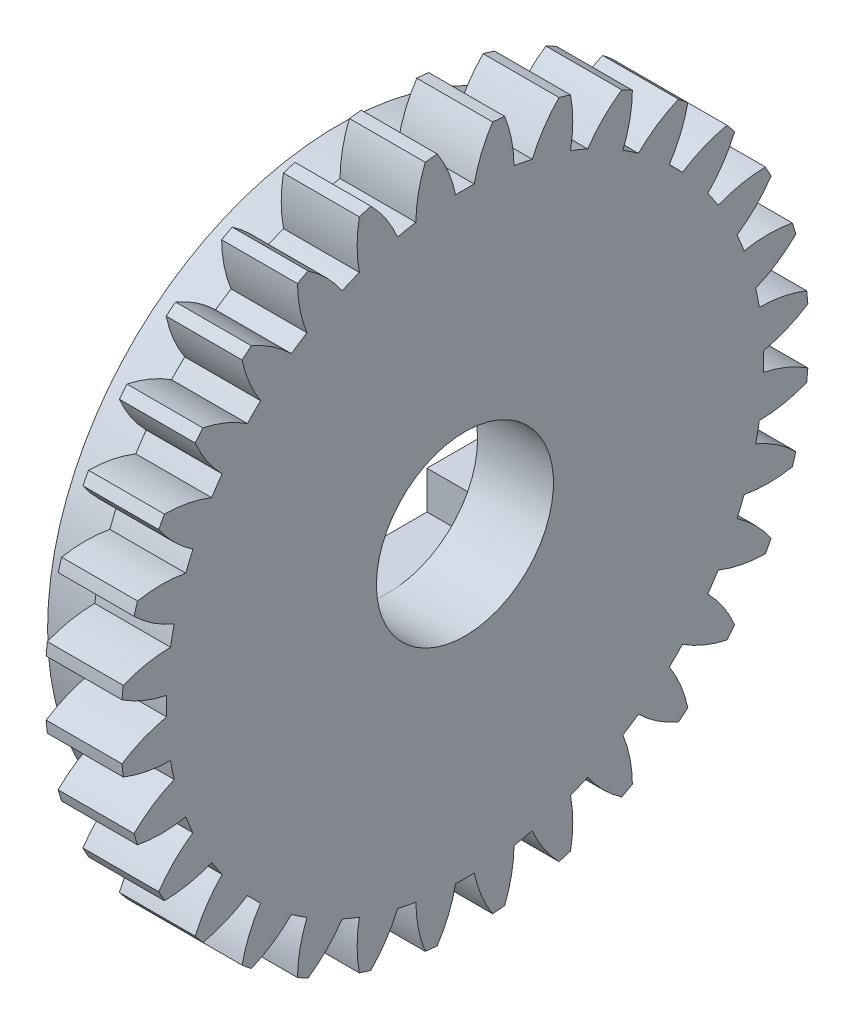
SolidWorks part; units mm, degrees
ref_plane "Plane1" through (0, 0, 0) normal (0, 0, 1) x (1, 0, 0)
ref_plane "Plane2" through (0, 0, 0) normal (0, 1, 0) x (1, 0, 0)
ref_plane "Plane3" through (0, 0, 0) normal (1, 0, 0) x (0, 0, -1)
other "Configuration Table"
sketch "HoldingSke" plane through (0, 0, 0) normal (0, 1, 0) x (1, 0, 0)
  line L0 (0, 0) -> (1.0601, -0.6624)
  line L1 (-15, 0) -> (100, 0) construction
  line L2 (0, 0) -> (-2.1039, 2.3779)
  line L3 (0, 0) -> (-11.863, 4.5341)
  line L4 (0, 0) -> (7.3237, 4.5764)
  line L5 (0, 0) -> (-46.8476, -17.4728)
  line L6 (0, 0) -> (-2.4869, -1.6779)
  line L7 (-2.1039, 2.3779) -> (8.6586, 51.2059)
  line L8 (-76.2, 54.61) -> (-76.1, 54.61)
  line L9 (-71.009, 38.7566) -> (-53.1078, 45.2721)
  line L10 (-76.2, 71.12) -> (104.1128, 71.12)
  line L11 (0, 0) -> (-3, 0)
  line L12 (-76.2, 101.6) -> (-76.17, 101.6)
  line L13 (24.9733, 27.94) -> (52.9518, 28.4284)
  line L14 (24.9733, 27.94) -> (24.9743, 27.94)
  line L15 (24.9733, 27.94) -> (100.4006, 29.5858)
  line L16 (-63.627, -0.8) -> (-12.827, -0.8)
  circle A0 centre (0, 0) radius 0.5
  circle A1 centre (0, 0) radius 11.799
  circle A2 centre (0, 0) radius 37.5
  circle A3 centre (0, 0) radius 0.5
  dimension "MHD" = 23.598
  dimension "Hub_dia" = 75
  dimension "Bore" = 1
  dimension "MBD" = 1
  dimension "Num_teeth" = 32
  dimension "Pitch" = 1.25
  dimension "Overall_len" = 50
  dimension "Show_teeth" = 32
  dimension "Thickness" = 3
  dimension "OAL" = 50.0001
  dimension "T_dim" = 0.1
  dimension "Ap" = 20
  dimension "H" = 19.05
  dimension "Pitch_radius" = 180.3128
  dimension "Width" = 3
  dimension "Backlash" = 0.03
  dimension "Addendum_fac" = 1
  dimension "Dedendum_fac" = 1.25
  dimension "Clearance_fac" = 0.25
  dimension "Dedendum_add" = 0.001
  dimension "Module" = 0.8
sketch "BasProSke" plane through (0, 0, 0) normal (0, 1, 0) x (1, 0, 0)
  line L0 (-10, 0) -> (60, 0) construction
  line L1 (0, 0) -> (0, 13.6)
  line L2 (0, 0) -> (3, 0)
  line L3 (3, 0) -> (3, 13.6)
  line L4 (3, 13.6) -> (0, 13.6)
  dimension "Thickness" = 3
  dimension "Diameter" = 27.2
revolve "Base-Revolve" add sketch "BasProSke" angle 360 about L0
sketch "TooCutSke" plane through (0, 0, 0) normal (1, 0, 0) x (0, 0, -1)
  line L1 (0, 0) -> (0, 107) construction
  line L2 (0, 0) -> (-0.6806, 12.7819) construction
  line L3 (0, 0) -> (-2.5067, 25.451) construction
  line L4 (-0.6806, 12.7819) -> (-1.2534, 12.7255) construction
  arc A0 (0.3689, 11.7932) -> (-0.3689, 11.7932) centre (0, 0) ccw
  arc A1 (1.1118, 13.58) -> (-1.1118, 13.58) centre (0, 0) ccw
  circle A2 centre (0, 0) radius 12.8 construction
  circle A3 centre (0, 0) radius 12.0281 construction
  arc A4 (-0.3689, 11.7932) -> (-1.1118, 13.58) centre (-5.3829, 10.7564) ccw
  arc A5 (1.1118, 13.58) -> (0.3689, 11.7932) centre (5.3829, 10.7564) ccw
  dimension "Root_dia" = 23.598
  dimension "Overcut_dia" = 27.2508
  dimension "Pitch_dia" = 25.6
  dimension "Base_dia" = 24.0561
  dimension "Flank_rad" = 5.12
  dimension "Half_ang" = 5.625
  dimension "Half_CT" = 0.5756
extrude "ToothCut" cut sketch "TooCutSke" along normal through all
fillet "Breaks" [suppressed] radius 0.016 tangent propagation no
fillet "RootFillets" [suppressed] radius 0.201
pattern_circular "TeethCuts" count 32 every 11.25 about axis through (-10, 0, 0) along (1, 0, 0) of "ToothCut", "RootFillets", "Breaks"
sketch "HubNeaOneSke" plane through (0, 0, 0) normal (-1, 0, 0) x (0, 0, 1)
  circle A0 centre (0, 0) radius 11.799
  dimension "Diameter" = 23.598
extrude "HubNearOne" [suppressed] add sketch "HubNeaOneSke" along normal blind 47.0001
sketch "HubNeaBotSke" plane through (0, 0, 0) normal (-1, 0, 0) x (0, 0, 1)
  circle A0 centre (0, 0) radius 11.799
  dimension "Diameter" = 23.598
extrude "HubNearBoth" [suppressed] add sketch "HubNeaBotSke" along normal blind 23.5
ref_plane "FarPln" through (3, 0, 0) normal (1, 0, 0) x (0, 0, -1)
sketch "HubFarSke" plane through (3, 0, 0) normal (1, 0, 0) x (0, 0, -1)
  circle A0 centre (0, 0) radius 11.799
  dimension "Diameter" = 23.598
extrude "HubFar" [suppressed] add sketch "HubFarSke" along normal blind 23.5
sketch "BorSke" plane through (0, 0, 0) normal (1, 0, 0) x (0, 0, -1)
  circle A0 centre (0, 0) radius 0.5
  dimension "Diameter" = 1
extrude "Bore" cut sketch "BorSke" along normal mid plane 100.0001
sketch "KeySke" plane through (0, 0, 0) normal (1, 0, 0) x (0, 0, -1)
  line L0 (-0.05, 0) -> (-0.05, 0.6)
  line L1 (-0.05, 0.6) -> (0.05, 0.6)
  line L2 (0.05, 0.6) -> (0.05, 0)
  line L3 (0, 0) -> (0, 34) construction
  line L4 (-0.05, 0) -> (0.05, 0)
  dimension "Offset" = 0.6
extrude "Keyway" [suppressed] cut sketch "KeySke" along normal mid plane 100.0001
pattern_circular "Keyway2" [suppressed] count 2 every 90 about axis through (-10, 0, 0) along (1, 0, 0) reverse direction yes
ref_axis "基准轴1" through (0, 0, 0) along (1, 0, 0)
sketch "草图2" plane through (0, 0, 0) normal (1, 0, 0) x (0, 0, -1)
  circle A1 centre (0, 0) radius 11.5
  dimension "D2" = 23
extrude "凸台-拉伸1" add sketch "草图2" against normal blind 2
sketch "草图1" plane through (-2, 0, 0) normal (1, 0, 0) x (0, 0, -1)
  line L0 (-6.3, 0) -> (6.3, 0) construction
  line L2 (-3.5, 3.5) -> (3.5, 3.5)
  line L3 (-3.5, 3.5) -> (-3.5, -3.5)
  line L4 (-3.5, -3.5) -> (3.5, -3.5)
  line L5 (3.5, 3.5) -> (3.5, -3.5)
  line L6 (-3.5, 3.5) -> (3.5, -3.5) construction
  line L7 (-3.5, -3.5) -> (3.5, 3.5) construction
  line L8 (-6.3, 2) -> (6.3, 2)
  line L9 (-6.3, -2) -> (6.3, -2)
  arc A9 (-6.3, 2) -> (-6.3, -2) centre (-6.3, 0) ccw
  arc A10 (6.3, -2) -> (6.3, 2) centre (6.3, 0) ccw
  point P0 (0, 0)
  point P8 (0, 0)
  point P13 (15.8938, 0)
  point P14 (0, 0)
  point P15 (8.3, 0)
  point P16 (0, 0)
  point P17 (0, 0)
  point P18 (-8.3, 0)
  dimension "D1" = 7
  dimension "D2" = 4
  dimension "D3" = 16.6
extrude "切除-拉伸1" cut sketch "草图1" along normal blind 2 contours L8 L3 L2 L5 | A10 L9 L5 L8 | L9 L3 L8 L5 | A9 L8 L3 L9 | L3 L9 L5 L4 region at (-2, 2.75, 0) region at (-2, 0, 0) region at (-2, 0, 5.7082) region at (-2, 0, -5.7082) region at (-2, -2.75, 0)
sketch "草图3" plane through (0, 0, 0) normal (-1, 0, 0) x (0, 0, 1)
  circle A0 centre (0, 0) radius 3.5
  dimension "D1" = 7
extrude "切除-拉伸2" cut sketch "草图3" against normal through all
equation "' \"Module@HoldingSke\" = 6.35"
equation "' \"Num_teeth@HoldingSke\" = 12"
equation "' \"Ap@HoldingSke\" =  20"
equation "' \"Ap@HoldingSke\" = 20"
equation "' \"Width@HoldingSke\" = 0.5 * 25.4"
equation "' \"Hub_dia@HoldingSke\"= 1 * 25.4"
equation "' \"Hub_dia@HoldingSke\" = 1 * 25.4"
equation "' \"Overall_len@HoldingSke\" = 1.0 * 25.4"
equation "' \"Bore@HoldingSke\" = 0.75 * 25.4"
equation "' \"T_dim@HoldingSke\" = 0.1 * 25.4"
equation "' \"Width@KeySke\" = 0.25 * 25.4"
equation "' \"Show_teeth@HoldingSke\" = 13"
equation "' \"Backlash@HoldingSke\" = 0.009 * 25.4"
equation "' \"Addendum_fac@HoldingSke\" = 1.0"
equation "' \"Dedendum_fac@HoldingSke\" = 1.25"
equation "' \"Dedendum_add@HoldingSke\" = 0.00005 * 25.4"
equation "' \"Clearance_fac@HoldingSke\" = 0.25"
equation "\"Pitch@HoldingSke\" = 1 / \"Module@HoldingSke\""
equation "\"Overcut_dia@TooCutSke\" = (\"Num_teeth@HoldingSke\" + 2 * \"Addendum_fac@HoldingSke\") / \"Pitch@HoldingSke\" + 0.002 * 25.4"
equation "\"Pitch_dia@TooCutSke\" = \"Num_teeth@HoldingSke\" / \"Pitch@HoldingSke\""
equation "\"Base_dia@TooCutSke\" = \"Num_teeth@HoldingSke\" / \"Pitch@HoldingSke\" * cos((\"Ap@HoldingSke\"  * 3.14159265 / 180))"
equation "\"Root_dia@TooCutSke\" = (\"Num_teeth@HoldingSke\" + 2) / \"Pitch@HoldingSke\" - 2 * (\"Addendum_fac@HoldingSke\" + \"Dedendum_fac@HoldingSke\") / \"Pitch@HoldingSke\" - \"Dedendum_add@HoldingSke\" * 2"
equation "\"Half_ang@TooCutSke\" = 180 / \"Num_teeth@HoldingSke\""
equation "\"Half_CT@TooCutSke\" = \"Num_teeth@HoldingSke\" / \"Pitch@HoldingSke\" * sin((3.14159265 / 2 / \"Num_teeth@HoldingSke\")) / 2 - 7 * \"Backlash@HoldingSke\" / 4"
equation "\"Flank_rad@TooCutSke\" = \"Num_teeth@HoldingSke\" / \"Pitch@HoldingSke\" / 5"
equation "\"Radius@RootFillets\" = \"Clearance_fac@HoldingSke\" / \"Pitch@HoldingSke\" + \"Dedendum_add@HoldingSke\""
equation "\"Break_rad@Breaks\" = 0.02 / \"Pitch@HoldingSke\""
equation "\"Thickness@HoldingSke\" = \"Width@HoldingSke\""
equation "\"OAL@HoldingSke\" = \"Thickness@HoldingSke\""
equation "\"MHD@HoldingSke\" = (\"Num_teeth@HoldingSke\" + 2) / \"Pitch@HoldingSke\" - 2 * (\"Addendum_fac@HoldingSke\" + \"Dedendum_fac@HoldingSke\")  / \"Pitch@HoldingSke\" - \"Dedendum_add@HoldingSke\" * 2"
equation "\"MBD@HoldingSke\" = (\"Num_teeth@HoldingSke\" + 2) / \"Pitch@HoldingSke\" - 2 * (\"Addendum_fac@HoldingSke\" + \"Dedendum_fac@HoldingSke\")  / \"Pitch@HoldingSke\" - \"Dedendum_add@HoldingSke\" * 2 - 0.002 * 25.4"
equation "\"MHD@HoldingSke\" = ((sgn( \"MHD@HoldingSke\" - \"Hub_dia@HoldingSke\" )-1)*( \"MHD@HoldingSke\" - \"Hub_dia@HoldingSke\" ))/-2+ \"Hub_dia@HoldingSke\""
equation "\"MBD@HoldingSke\" = ((sgn( \"MBD@HoldingSke\" - \"Bore@HoldingSke\" )-1)*( \"MBD@HoldingSke\" - \"Bore@HoldingSke\" ))/-2+ \"Bore@HoldingSke\""
equation "\"OAL@HoldingSke\" = ((sgn( \"OAL@HoldingSke\" - \"Overall_len@HoldingSke\" )+1)*( \"OAL@HoldingSke\" - \"Overall_len@HoldingSke\" ))/2 + \"Overall_len@HoldingSke\" + 0.000002 * 25.4"
equation "\"Num_teeth@TeethCuts\" = int( \"Show_teeth@HoldingSke\" ) + 1"
equation "\"Num_teeth@TeethCuts\" = ((sgn( \"Num_teeth@TeethCuts\" - \"Num_teeth@HoldingSke\" )-1)*( \"Num_teeth@TeethCuts\" - \"Num_teeth@HoldingSke\" ))/-2+ \"Num_teeth@HoldingSke\""
equation "\"Num_teeth@TeethCuts\" = ((sgn( \"Num_teeth@TeethCuts\" - 2.0)+1)*( \"Num_teeth@TeethCuts\" - 2.0))/2 +2.0"
equation "\"Angle@TeethCuts\" = 360.0 / \"Num_teeth@HoldingSke\""
equation "\"Diameter@BasProSke\" = (\"Num_teeth@HoldingSke\" + 2 * \"Addendum_fac@HoldingSke\") / \"Pitch@HoldingSke\""
equation "\"Thickness@BasProSke\"  = \"Thickness@HoldingSke\""
equation "' \"Fillet_rad@BasProSke\" =  \"Thickness@HoldingSke\" * 0.05"
equation "' \"Fillet_rad@BasProSke\" = \"Thickness@HoldingSke\" * 0.05"
equation "\"MHD@HoldingSke\" = ((sgn( \"MHD@HoldingSke\" - \"Root_dia@TooCutSke\" )-1)*( \"MHD@HoldingSke\" - \"Root_dia@TooCutSke\" ))/-2+ \"Root_dia@TooCutSke\""
equation "\"Diameter@HubNeaOneSke\" = \"MHD@HoldingSke\""
equation "\"Length@HubNearOne\" = \"OAL@HoldingSke\" - \"Thickness@BasProSke\""
equation "\"Diameter@HubNeaBotSke\" = \"MHD@HoldingSke\""
equation "\"Length@HubNearBoth\" = ( \"OAL@HoldingSke\" - \"Thickness@BasProSke\" ) / 2.0"
equation "\"Thickness@FarPln\" = \"Thickness@BasProSke\""
equation "\"Diameter@HubFarSke\" = \"MHD@HoldingSke\""
equation "\"Length@HubFar\" = ( \"OAL@HoldingSke\" - \"Thickness@BasProSke\" ) / 2.0"
equation "\"Diameter@BorSke\" = \"MBD@HoldingSke\""
equation "\"D1@Bore\" = \"OAL@HoldingSke\" * 2.0"
equation "\"D1@Keyway\" = \"OAL@HoldingSke\" * 2.0"
equation "\"Offset@KeySke\" = \"T_dim@HoldingSke\" + \"MBD@HoldingSke\" / 2.0"
